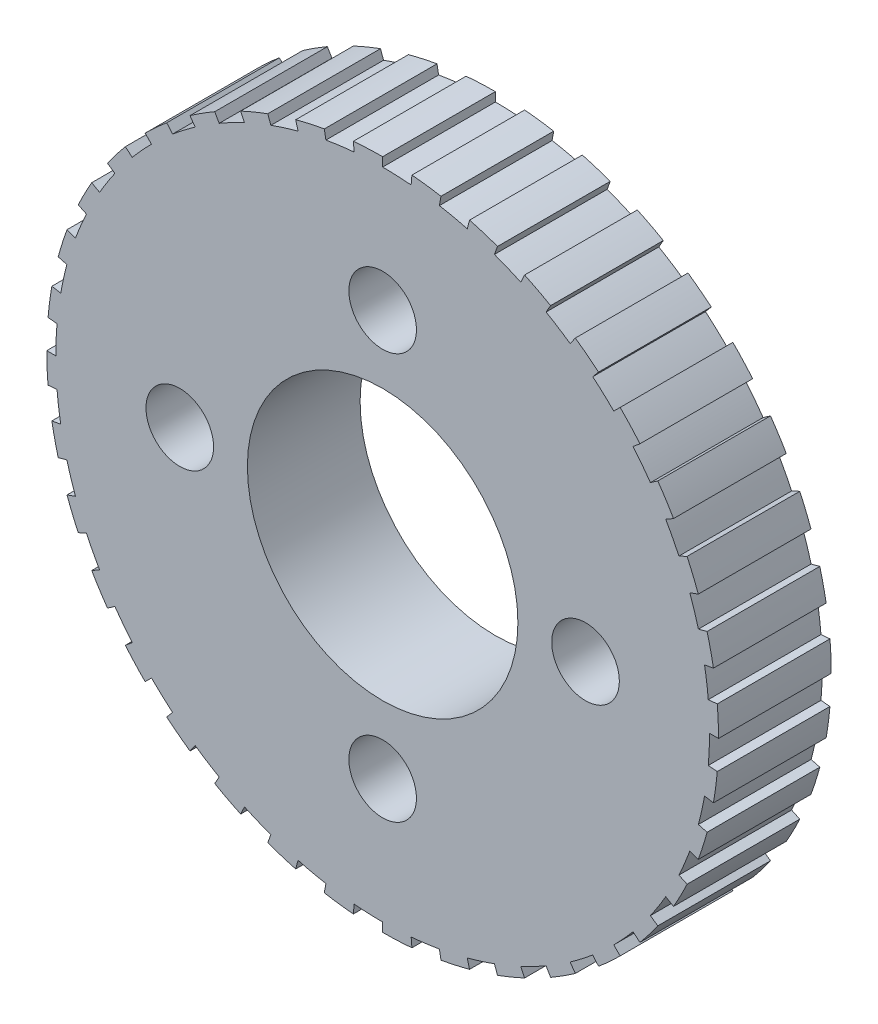
SolidWorks part; units mm, degrees
ref_plane "Front" through (0, 0, 0) normal (0, 0, 1) x (1, 0, 0)
ref_plane "Top" through (0, 0, 0) normal (0, 1, 0) x (1, 0, 0)
ref_plane "Right" through (0, 0, 0) normal (1, 0, 0) x (0, 0, -1)
sketch "草图1" plane through (0, 0, 0) normal (0, 0, 1) x (1, 0, 0)
  line L0 (28.5594, -5.0358) -> (29.3473, -5.1747)
  line L1 (28.8896, -2.5275) -> (29.6866, -2.5972)
  line L2 (27.2511, -9.9186) -> (28.0028, -10.1922)
  line L3 (29, 0) -> (29.8, 0)
  line L4 (28.8896, 2.5275) -> (29.6866, 2.5972)
  line L5 (28.0118, -7.5058) -> (28.7846, -7.7128)
  line L6 (25.1147, -14.5) -> (25.8076, -14.9)
  line L7 (26.2829, -12.2559) -> (27.008, -12.594)
  line L8 (22.2153, -18.6408) -> (22.8281, -19.1551)
  line L9 (23.7554, -16.6337) -> (24.4107, -17.0926)
  line L10 (18.6408, -22.2153) -> (19.1551, -22.8281)
  line L11 (20.5061, -20.5061) -> (21.0718, -21.0718)
  line L12 (14.5, -25.1147) -> (14.9, -25.8076)
  line L13 (16.6337, -23.7554) -> (17.0926, -24.4107)
  line L14 (9.9186, -27.2511) -> (10.1922, -28.0028)
  line L15 (12.2559, -26.2829) -> (12.594, -27.008)
  line L16 (5.0358, -28.5594) -> (5.1747, -29.3473)
  line L17 (7.5058, -28.0118) -> (7.7128, -28.7846)
  line L18 (0, -29) -> (0, -29.8)
  line L19 (2.5275, -28.8896) -> (2.5972, -29.6866)
  line L20 (-5.0358, -28.5594) -> (-5.1747, -29.3473)
  line L21 (-2.5275, -28.8896) -> (-2.5972, -29.6866)
  line L22 (-9.9186, -27.2511) -> (-10.1922, -28.0028)
  line L23 (-7.5058, -28.0118) -> (-7.7128, -28.7846)
  line L24 (-14.5, -25.1147) -> (-14.9, -25.8076)
  line L25 (-12.2559, -26.2829) -> (-12.594, -27.008)
  line L26 (-18.6408, -22.2153) -> (-19.1551, -22.8281)
  line L27 (-16.6337, -23.7554) -> (-17.0926, -24.4107)
  line L28 (-22.2153, -18.6408) -> (-22.8281, -19.1551)
  line L29 (-20.5061, -20.5061) -> (-21.0718, -21.0718)
  line L30 (-25.1147, -14.5) -> (-25.8076, -14.9)
  line L31 (-23.7554, -16.6337) -> (-24.4107, -17.0926)
  line L32 (-27.2511, -9.9186) -> (-28.0028, -10.1922)
  line L33 (-26.2829, -12.2559) -> (-27.008, -12.594)
  line L34 (-28.5594, -5.0358) -> (-29.3473, -5.1747)
  line L35 (-28.0118, -7.5058) -> (-28.7846, -7.7128)
  line L36 (-29, 0) -> (-29.8, 0)
  line L37 (-28.8896, -2.5275) -> (-29.6866, -2.5972)
  line L38 (-28.5594, 5.0358) -> (-29.3473, 5.1747)
  line L39 (-28.8896, 2.5275) -> (-29.6866, 2.5972)
  line L40 (-27.2511, 9.9186) -> (-28.0028, 10.1922)
  line L41 (-28.0118, 7.5058) -> (-28.7846, 7.7128)
  line L42 (-25.1147, 14.5) -> (-25.8076, 14.9)
  line L43 (-26.2829, 12.2559) -> (-27.008, 12.594)
  line L44 (-22.2153, 18.6408) -> (-22.8281, 19.1551)
  line L45 (-23.7554, 16.6337) -> (-24.4107, 17.0926)
  line L46 (-18.6408, 22.2153) -> (-19.1551, 22.8281)
  line L47 (-20.5061, 20.5061) -> (-21.0718, 21.0718)
  line L48 (-14.5, 25.1147) -> (-14.9, 25.8076)
  line L49 (-16.6337, 23.7554) -> (-17.0926, 24.4107)
  line L50 (-9.9186, 27.2511) -> (-10.1922, 28.0028)
  line L51 (-12.2559, 26.2829) -> (-12.594, 27.008)
  line L52 (-5.0358, 28.5594) -> (-5.1747, 29.3473)
  line L53 (-7.5058, 28.0118) -> (-7.7128, 28.7846)
  line L54 (0, 29) -> (0, 29.8)
  line L55 (-2.5275, 28.8896) -> (-2.5972, 29.6866)
  line L56 (5.0358, 28.5594) -> (5.1747, 29.3473)
  line L57 (2.5275, 28.8896) -> (2.5972, 29.6866)
  line L58 (9.9186, 27.2511) -> (10.1922, 28.0028)
  line L59 (7.5058, 28.0118) -> (7.7128, 28.7846)
  line L60 (14.5, 25.1147) -> (14.9, 25.8076)
  line L61 (12.2559, 26.2829) -> (12.594, 27.008)
  line L62 (18.6408, 22.2153) -> (19.1551, 22.8281)
  line L63 (16.6337, 23.7554) -> (17.0926, 24.4107)
  line L64 (22.2153, 18.6408) -> (22.8281, 19.1551)
  line L65 (20.5061, 20.5061) -> (21.0718, 21.0718)
  line L66 (25.1147, 14.5) -> (25.8076, 14.9)
  line L67 (23.7554, 16.6337) -> (24.4107, 17.0926)
  line L68 (27.2511, 9.9186) -> (28.0028, 10.1922)
  line L69 (26.2829, 12.2559) -> (27.008, 12.594)
  line L70 (28.5594, 5.0358) -> (29.3473, 5.1747)
  line L71 (28.0118, 7.5058) -> (28.7846, 7.7128)
  circle A0 centre (0, 0) radius 12
  arc A1 (29.8, 0) -> (29.6866, 2.5972) centre (0, 0) ccw
  arc A2 (28.8896, 2.5275) -> (28.5594, 5.0358) centre (0, 0) ccw
  arc A3 (29.3473, -5.1747) -> (29.6866, -2.5972) centre (0, 0) ccw
  arc A4 (28.8896, -2.5275) -> (29, 0) centre (0, 0) ccw
  arc A5 (28.0028, -10.1922) -> (28.7846, -7.7128) centre (0, 0) ccw
  arc A6 (28.0118, -7.5058) -> (28.5594, -5.0358) centre (0, 0) ccw
  arc A7 (25.8076, -14.9) -> (27.008, -12.594) centre (0, 0) ccw
  arc A8 (26.2829, -12.2559) -> (27.2511, -9.9186) centre (0, 0) ccw
  arc A9 (22.8281, -19.1551) -> (24.4107, -17.0926) centre (0, 0) ccw
  arc A10 (23.7554, -16.6337) -> (25.1147, -14.5) centre (0, 0) ccw
  arc A11 (19.1551, -22.8281) -> (21.0718, -21.0718) centre (0, 0) ccw
  arc A12 (20.5061, -20.5061) -> (22.2153, -18.6408) centre (0, 0) ccw
  arc A13 (14.9, -25.8076) -> (17.0926, -24.4107) centre (0, 0) ccw
  arc A14 (16.6337, -23.7554) -> (18.6408, -22.2153) centre (0, 0) ccw
  arc A15 (10.1922, -28.0028) -> (12.594, -27.008) centre (0, 0) ccw
  arc A16 (12.2559, -26.2829) -> (14.5, -25.1147) centre (0, 0) ccw
  arc A17 (5.1747, -29.3473) -> (7.7128, -28.7846) centre (0, 0) ccw
  arc A18 (7.5058, -28.0118) -> (9.9186, -27.2511) centre (0, 0) ccw
  arc A19 (0, -29.8) -> (2.5972, -29.6866) centre (0, 0) ccw
  arc A20 (2.5275, -28.8896) -> (5.0358, -28.5594) centre (0, 0) ccw
  arc A21 (-5.1747, -29.3473) -> (-2.5972, -29.6866) centre (0, 0) ccw
  arc A22 (-2.5275, -28.8896) -> (0, -29) centre (0, 0) ccw
  arc A23 (-10.1922, -28.0028) -> (-7.7128, -28.7846) centre (0, 0) ccw
  arc A24 (-7.5058, -28.0118) -> (-5.0358, -28.5594) centre (0, 0) ccw
  arc A25 (-14.9, -25.8076) -> (-12.594, -27.008) centre (0, 0) ccw
  arc A26 (-12.2559, -26.2829) -> (-9.9186, -27.2511) centre (0, 0) ccw
  arc A27 (-19.1551, -22.8281) -> (-17.0926, -24.4107) centre (0, 0) ccw
  arc A28 (-16.6337, -23.7554) -> (-14.5, -25.1147) centre (0, 0) ccw
  arc A29 (-22.8281, -19.1551) -> (-21.0718, -21.0718) centre (0, 0) ccw
  arc A30 (-20.5061, -20.5061) -> (-18.6408, -22.2153) centre (0, 0) ccw
  arc A31 (-25.8076, -14.9) -> (-24.4107, -17.0926) centre (0, 0) ccw
  arc A32 (-23.7554, -16.6337) -> (-22.2153, -18.6408) centre (0, 0) ccw
  arc A33 (-28.0028, -10.1922) -> (-27.008, -12.594) centre (0, 0) ccw
  arc A34 (-26.2829, -12.2559) -> (-25.1147, -14.5) centre (0, 0) ccw
  arc A35 (-29.3473, -5.1747) -> (-28.7846, -7.7128) centre (0, 0) ccw
  arc A36 (-28.0118, -7.5058) -> (-27.2511, -9.9186) centre (0, 0) ccw
  arc A37 (-29.8, 0) -> (-29.6866, -2.5972) centre (0, 0) ccw
  arc A38 (-28.8896, -2.5275) -> (-28.5594, -5.0358) centre (0, 0) ccw
  arc A39 (-29.3473, 5.1747) -> (-29.6866, 2.5972) centre (0, 0) ccw
  arc A40 (-28.8896, 2.5275) -> (-29, 0) centre (0, 0) ccw
  arc A41 (-28.0028, 10.1922) -> (-28.7846, 7.7128) centre (0, 0) ccw
  arc A42 (-28.0118, 7.5058) -> (-28.5594, 5.0358) centre (0, 0) ccw
  arc A43 (-25.8076, 14.9) -> (-27.008, 12.594) centre (0, 0) ccw
  arc A44 (-26.2829, 12.2559) -> (-27.2511, 9.9186) centre (0, 0) ccw
  arc A45 (-22.8281, 19.1551) -> (-24.4107, 17.0926) centre (0, 0) ccw
  arc A46 (-23.7554, 16.6337) -> (-25.1147, 14.5) centre (0, 0) ccw
  arc A47 (-19.1551, 22.8281) -> (-21.0718, 21.0718) centre (0, 0) ccw
  arc A48 (-20.5061, 20.5061) -> (-22.2153, 18.6408) centre (0, 0) ccw
  arc A49 (-14.9, 25.8076) -> (-17.0926, 24.4107) centre (0, 0) ccw
  arc A50 (-16.6337, 23.7554) -> (-18.6408, 22.2153) centre (0, 0) ccw
  arc A51 (-10.1922, 28.0028) -> (-12.594, 27.008) centre (0, 0) ccw
  arc A52 (-12.2559, 26.2829) -> (-14.5, 25.1147) centre (0, 0) ccw
  arc A53 (-5.1747, 29.3473) -> (-7.7128, 28.7846) centre (0, 0) ccw
  arc A54 (-7.5058, 28.0118) -> (-9.9186, 27.2511) centre (0, 0) ccw
  arc A55 (0, 29.8) -> (-2.5972, 29.6866) centre (0, 0) ccw
  arc A56 (-2.5275, 28.8896) -> (-5.0358, 28.5594) centre (0, 0) ccw
  arc A57 (5.1747, 29.3473) -> (2.5972, 29.6866) centre (0, 0) ccw
  arc A58 (2.5275, 28.8896) -> (0, 29) centre (0, 0) ccw
  arc A59 (10.1922, 28.0028) -> (7.7128, 28.7846) centre (0, 0) ccw
  arc A60 (7.5058, 28.0118) -> (5.0358, 28.5594) centre (0, 0) ccw
  arc A61 (14.9, 25.8076) -> (12.594, 27.008) centre (0, 0) ccw
  arc A62 (12.2559, 26.2829) -> (9.9186, 27.2511) centre (0, 0) ccw
  arc A63 (19.1551, 22.8281) -> (17.0926, 24.4107) centre (0, 0) ccw
  arc A64 (16.6337, 23.7554) -> (14.5, 25.1147) centre (0, 0) ccw
  arc A65 (22.8281, 19.1551) -> (21.0718, 21.0718) centre (0, 0) ccw
  arc A66 (20.5061, 20.5061) -> (18.6408, 22.2153) centre (0, 0) ccw
  arc A67 (25.8076, 14.9) -> (24.4107, 17.0926) centre (0, 0) ccw
  arc A68 (23.7554, 16.6337) -> (22.2153, 18.6408) centre (0, 0) ccw
  arc A69 (28.0028, 10.1922) -> (27.008, 12.594) centre (0, 0) ccw
  arc A70 (26.2829, 12.2559) -> (25.1147, 14.5) centre (0, 0) ccw
  arc A71 (29.3473, 5.1747) -> (28.7846, 7.7128) centre (0, 0) ccw
  arc A72 (28.0118, 7.5058) -> (27.2511, 9.9186) centre (0, 0) ccw
  point P10 (0, 0)
  point P186 (0, 0)
  dimension "D1" = 36
extrude "凸台-拉伸1" add sketch "草图1" along normal blind 5 and the other way blind 5
sketch "草图2" plane through (0, 0, 0) normal (0, 0, 1) x (1, 0, 0)
  circle A0 centre (18, 0) radius 3
  circle A1 centre (0, -18) radius 3
  circle A2 centre (-18, 0) radius 3
  circle A3 centre (0, 18) radius 3
  point P11 (0, 0)
  dimension "D1" = 4
extrude "切除-拉伸1" cut sketch "草图2" against normal blind 10 and the other way blind 10
